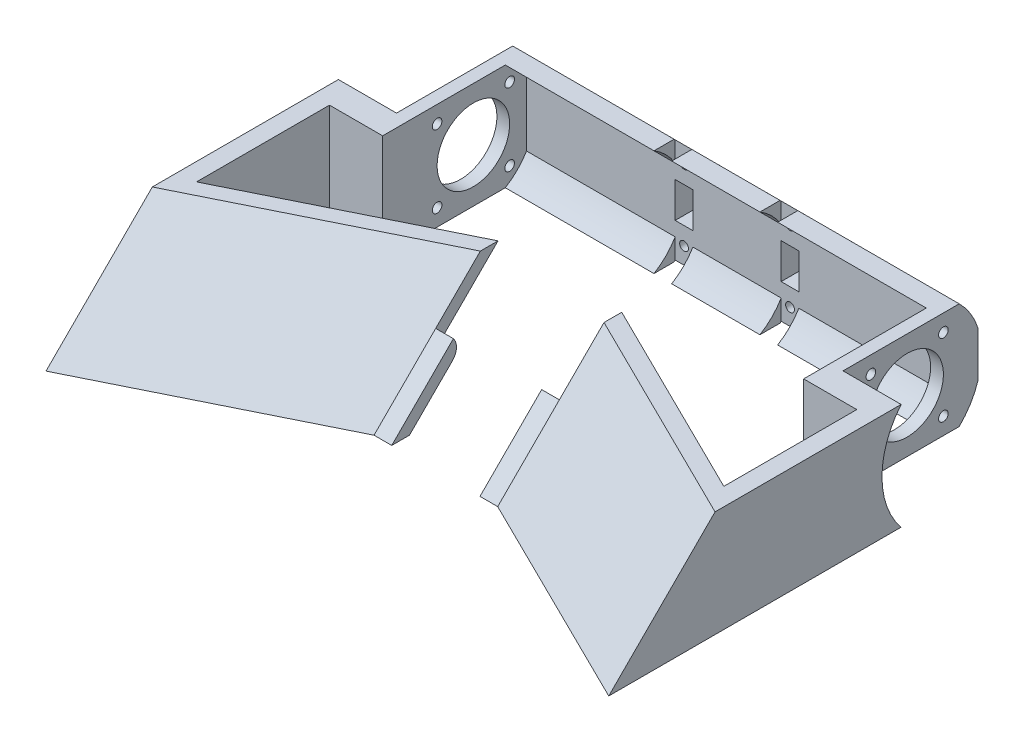
SolidWorks part; units mm, degrees
ref_plane "Front Plane" through (0, 0, 0) normal (0, 0, 1) x (1, 0, 0)
ref_plane "Top Plane" through (0, 0, 0) normal (0, 1, 0) x (1, 0, 0)
ref_plane "Right Plane" through (0, 0, 0) normal (1, 0, 0) x (0, 0, -1)
sketch "Sketch3" plane through (0, 0, 0) normal (0, 1, 0) x (1, 0, 0)
  line L0 (0, 3.175) -> (0, -37.667) construction
  line L1 (-80.01, 3.175) -> (80.01, 3.175)
  line L2 (-80.01, 3.175) -> (-80.01, -3.175)
  line L3 (-80.01, -3.175) -> (80.01, -3.175)
  line L4 (80.01, 3.175) -> (80.01, -3.175)
  line L5 (-80.01, 3.175) -> (80.01, -3.175) construction
  line L6 (-80.01, -3.175) -> (80.01, 3.175) construction
  line L7 (100.838, -54.737) -> (100.838, -48.387)
  line L8 (-80.01, 3.175) -> (-75.438, 3.175)
  line L9 (-80.01, 3.175) -> (-80.01, -54.737)
  line L10 (-80.01, -54.737) -> (-75.438, -54.737)
  line L11 (-75.438, 3.175) -> (-75.438, -54.737)
  line L12 (-75.438, -54.737) -> (-100.838, -54.737)
  line L13 (-75.438, -54.737) -> (-75.438, -48.387)
  line L14 (-75.438, -48.387) -> (-100.838, -48.387)
  line L15 (-100.838, -54.737) -> (-100.838, -48.387)
  line L16 (75.438, -48.387) -> (100.838, -48.387)
  line L17 (75.438, -54.737) -> (75.438, -48.387)
  line L18 (75.438, -54.737) -> (100.838, -54.737)
  line L19 (75.438, 3.175) -> (75.438, -54.737)
  line L20 (80.01, -54.737) -> (75.438, -54.737)
  line L21 (80.01, 3.175) -> (80.01, -54.737)
  point P0 (0, 0)
  dimension "D1" = 6.35
  dimension "D2" = 160.02
  dimension "D3" = 4.572
  dimension "D4" = 57.912
  dimension "D5" = 25.4
  dimension "D6" = 6.35
extrude "Boss-Extrude1" add sketch "Sketch3" along normal blind 38.1 contours L15 L12 L9 L14 | L11 L14 L9 L10 | L14 L11 L3 L9 | L11 L1 L2 L3 | L19 L1 L11 L3 | L1 L19 L3 L4 | L21 L3 L19 L16 | L21 L16 L17 L18 | L16 L21 L18 L7 region at (-77.724, 0, 0) region at (0, 0, 0) region at (-77.724, 0, 25.781) region at (77.724, 0, 0) region at (-77.724, 0, 51.562) region at (-90.424, 0, 51.562) region at (77.724, 0, 25.781) region at (77.724, 0, 51.562) region at (90.424, 0, 51.562)
sketch "Sketch5" plane through (-80.01, 0, 0) normal (-1, 0, 0) x (0, 0, 1)
  line L0 (-3.175, 0) -> (48.387, 0) construction
  line L1 (-3.175, 38.1) -> (-3.175, 0) construction
  circle A0 centre (9.225, 32.05) radius 1.7272
  circle A1 centre (35.225, 32.05) radius 1.7272
  circle A2 centre (35.225, 6.05) radius 1.7272
  circle A3 centre (9.225, 6.05) radius 1.7272
  circle A4 centre (22.225, 19.05) radius 13
  dimension "D7" = 13
  dimension "D8" = 13
  dimension "D1" = 3.4544
  dimension "D2" = 26
  dimension "D3" = 26
  dimension "D4" = 26
  dimension "D5" = 13
  dimension "D6" = 13
  dimension "D9" = 19.05
  dimension "D10" = 13
  dimension "D11" = 25.4
extrude "Cut-Extrude2" cut sketch "Sketch5" against normal through all
sketch "Sketch6" plane through (-80.01, 0, 0) normal (-1, 0, 0) x (0, 0, 1)
  line L0 (22.225, 45.72) -> (-24.9442, 45.72)
  line L1 (-24.9442, 45.72) -> (-24.9442, -7.62)
  line L2 (-24.9442, -7.62) -> (22.225, -7.62)
  arc A0 (22.225, 45.72) -> (22.225, -7.62) centre (22.225, 19.05) ccw
  dimension "D1" = 53.34
extrude "Cut-Extrude3" cut sketch "Sketch6" against normal through all
sketch "Sketch7" plane through (-80.01, 0, 0) normal (-1, 0, 0) x (0, 0, 1)
  line L0 (3.5599, 38.1) -> (10.7774, 38.1)
  line L1 (3.5599, 38.1) -> (48.387, 38.1) construction
  line L2 (-3.175, 27.182) -> (-3.175, 10.918)
  line L3 (3.5599, 0) -> (10.7774, 0)
  arc A0 (10.7774, 38.1) -> (10.7774, 0) centre (22.225, 19.05) ccw
  arc A1 (3.5599, 38.1) -> (-3.175, 27.182) centre (22.225, 19.05) ccw
  arc A2 (-3.175, 10.918) -> (3.5599, 0) centre (22.225, 19.05) ccw
  dimension "D1" = 44.45
extrude "Boss-Extrude2" add sketch "Sketch7" against normal up to surface (155.448 mm away) up to face at (75.438, 32.05, 33.4978)
sketch "Sketch4" plane through (0, 0, 3.175) normal (0, 0, 1) x (1, 0, 0)
  line L0 (0, 0) -> (0, 38.1) construction
  line L1 (-75.438, 38.1) -> (75.438, 38.1) construction
  line L2 (22.1615, 12.7) -> (15.8115, 25.4) construction
  line L3 (-22.1615, 25.4) -> (-15.8115, 25.4)
  line L4 (-22.1615, 25.4) -> (-22.1615, 12.7)
  line L5 (-22.1615, 12.7) -> (-15.8115, 12.7)
  line L6 (-15.8115, 25.4) -> (-15.8115, 12.7)
  line L7 (-22.1615, 25.4) -> (-15.8115, 12.7) construction
  line L8 (-22.1615, 12.7) -> (-15.8115, 25.4) construction
  line L9 (22.1615, 25.4) -> (15.8115, 12.7) construction
  line L10 (15.8115, 25.4) -> (15.8115, 12.7)
  line L11 (22.1615, 12.7) -> (15.8115, 12.7)
  line L12 (22.1615, 25.4) -> (22.1615, 12.7)
  line L13 (22.1615, 25.4) -> (15.8115, 25.4)
  line L14 (-18.9865, 19.05) -> (18.9865, 19.05)
  line L15 (75.438, 38.1) -> (-75.438, 38.1) construction
  circle A0 centre (-18.9865, 31.75) radius 1.5875
  circle A1 centre (-18.9865, 6.35) radius 1.5875
  circle A2 centre (18.9865, 6.35) radius 1.5875
  circle A3 centre (18.9865, 31.75) radius 1.5875
  point P5 (-18.9865, 19.05)
  point P14 (18.9865, 19.05)
  dimension "D4" = 3.175
  dimension "D1" = 6.35
  dimension "D2" = 12.7
  dimension "D3" = 15.8115
  dimension "D5" = 6.35
  dimension "D6" = 19.05
extrude "Cut-Extrude1" cut sketch "Sketch4" against normal through all both and the other way through all contours L6 L3 L4 L5 | A0 | A1 | A3 | L12 L11 L10 L13 | A2 region at (-18.9865, 25.258, 3.175)
sketch "Sketch8" plane through (-80.01, 0, 0) normal (-1, 0, 0) x (0, 0, 1)
  circle A0 centre (22.225, 19.05) radius 29.845
  dimension "D1" = 59.69
extrude "Cut-Extrude4" cut sketch "Sketch8" along normal through all contours A0
sketch "Sketch9" plane through (-80.01, 0, 0) normal (-1, 0, 0) x (0, 0, 1)
  line L0 (48.387, 38.1) -> (48.387, 33.4122)
  line L1 (48.387, 38.1) -> (45.1994, 38.1)
  line L3 (48.387, 0) -> (48.387, 4.6878)
  line L4 (48.387, 0) -> (45.1994, 0)
  arc A0 (48.387, 33.4122) -> (45.1994, 38.1) centre (22.225, 19.05) ccw
  arc A1 (45.1994, 0) -> (48.387, 4.6878) centre (22.225, 19.05) ccw
extrude "Boss-Extrude3" add sketch "Sketch9" along normal blind 20.828
mirror "Mirror4" about plane through (0, 0, 0) normal (1, 0, 0) of "Boss-Extrude3", "Cut-Extrude4"
sketch "Sketch10" plane through (0, 0, 3.175) normal (0, 0, 1) x (1, 0, 0)
  line L0 (22.1615, 0) -> (15.8115, 38.1) construction
  line L3 (0, 30.4976) -> (0, 7.6024) construction
  line L4 (18.0109, 30.4976) -> (-18.0109, 30.4976) construction
  line L5 (-18.0109, 7.6024) -> (18.0109, 7.6024) construction
  line L6 (-22.1615, 25.4) -> (-15.8115, 12.7) construction
  line L7 (22.1615, 38.1) -> (15.8115, 0) construction
  line L8 (-22.1615, 38.1) -> (-15.8115, 38.1)
  line L9 (-22.1615, 38.1) -> (-22.1615, 0)
  line L10 (-22.1615, 0) -> (-15.8115, 0)
  line L11 (-15.8115, 38.1) -> (-15.8115, 0)
  line L12 (-22.1615, 38.1) -> (-15.8115, 0) construction
  line L13 (-22.1615, 0) -> (-15.8115, 38.1) construction
  line L14 (22.1615, 25.4) -> (15.8115, 12.7) construction
  line L15 (15.8115, 38.1) -> (15.8115, 0)
  line L16 (22.1615, 0) -> (15.8115, 0)
  line L17 (22.1615, 38.1) -> (22.1615, 0)
  line L18 (22.1615, 38.1) -> (15.8115, 38.1)
  point P16 (-18.9865, 19.05)
  point P21 (18.9865, 19.05)
  dimension "D1" = 6.35
  dimension "D2" = 38.1
extrude "Cut-Extrude5" cut sketch "Sketch10" along normal through all
sketch "Sketch11" plane through (-100.838, 0, 0) normal (-1, 0, 0) x (0, 0, 1)
  line L0 (143.637, 0) -> (105.537, 38.1)
  line L1 (54.737, 38.1) -> (105.537, 38.1)
  line L2 (54.737, 38.1) -> (54.737, 0)
  line L3 (54.737, 0) -> (143.637, 0)
  dimension "D1" = 88.9
  dimension "D2" = 45
  dimension "D3" = 38.1
extrude "Boss-Extrude4" add sketch "Sketch11" against normal blind 6.35
sketch "Sketch12" plane through (0, 0, 0) normal (0, -1, 0) x (1, 0, 0)
  line L0 (-22.1615, 10.7774) -> (-22.1615, 104.7574) construction
  line L1 (-22.1615, 104.7574) -> (-100.838, 143.637)
  dimension "D1" = 93.98
sketch "Sketch13" plane through (-100.838, 0, 0) normal (-1, 0, 0) x (0, 0, 1)
  line L0 (143.637, 0) -> (149.987, 0)
  line L1 (105.537, 38.1) -> (111.887, 38.1)
  line L2 (111.887, 38.1) -> (149.987, 0)
  line L3 (105.537, 38.1) -> (143.637, 0)
  dimension "D1" = 6.35
  dimension "D2" = 6.35
sweep "Sweep1" add profiles "Sketch13" path "Sketch12"
sketch "Sketch17" plane through (-22.1615, 0, 0) normal (1, 0, 0) x (0, 0, -1)
  line L1 (-82.6594, 22.098) -> (-104.7574, 0)
  line L2 (-104.7574, 0) -> (-111.1074, 0)
  line L3 (-111.1074, 0) -> (-89.0094, 22.098)
  line L4 (-89.0094, 22.098) -> (-82.6594, 22.098)
  dimension "D1" = 22.098
  dimension "D2" = 45
extrude "Boss-Extrude5" add sketch "Sketch17" along normal blind 6.35
fillet "Fillet1" radius 5.08 1 edges at (-18.9865, 22.098, 82.6594)
mirror "Mirror6" about plane through (0, 0, 0) normal (1, 0, 0) of "Fillet1", "Boss-Extrude5", "Sweep1", "Boss-Extrude4"
